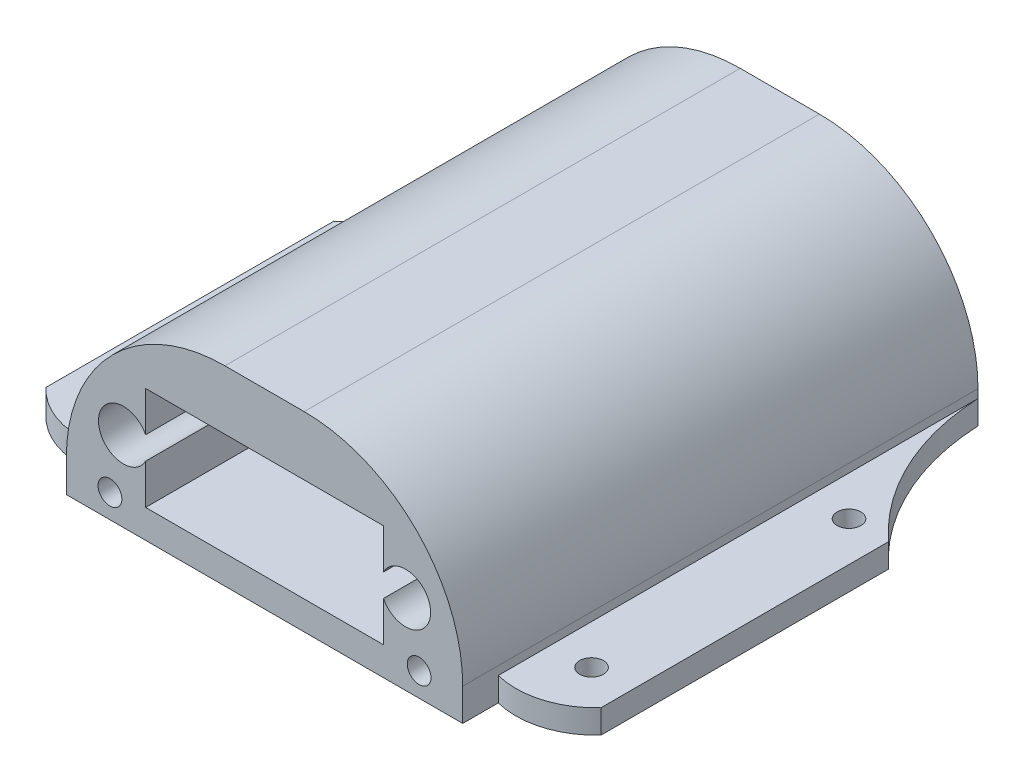
SolidWorks part; units mm, degrees
ref_plane "Front Plane" through (0, 0, 0) normal (0, 0, 1) x (1, 0, 0)
ref_plane "Top Plane" through (0, 0, 0) normal (0, 1, 0) x (1, 0, 0)
ref_plane "Right Plane" through (0, 0, 0) normal (1, 0, 0) x (0, 0, -1)
sketch "Sketch1" plane through (0, 0, 0) normal (0, 0, 1) x (1, 0, 0)
  line L0 (25, 10.1) -> (25, 3.6)
  line L1 (0, 0) -> (50, 0)
  line L2 (0, 0) -> (0, 4.0716)
  line L3 (20, 24.0716) -> (30, 24.0716)
  line L4 (50, 0) -> (50, 4.0716)
  line L10 (10, 16.6) -> (40, 16.6)
  line L11 (10, 16.6) -> (10, 3.6)
  line L12 (10, 3.6) -> (40, 3.6)
  line L13 (40, 16.6) -> (40, 3.6)
  line L14 (10, 16.6) -> (40, 3.6) construction
  line L15 (10, 3.6) -> (40, 16.6) construction
  arc A3 (30, 24.0716) -> (50, 4.0716) centre (30, 4.0716) cw
  arc A4 (0, 4.0716) -> (20, 24.0716) centre (20, 4.0716) cw
  arc A5 (40, 11.5431) -> (40, 8.6569) centre (42.8, 10.1) cw
  arc A6 (10, 11.5431) -> (10, 8.6569) centre (7.2, 10.1) ccw
  point P7 (50, 24.0716)
  point P9 (25, 10.1)
  dimension "D5" = 13
  dimension "D6" = 30
  dimension "D4" = 20
  dimension "D1" = 50
  dimension "D2" = 3.6
  dimension "D7" = 0
extrude "Boss-Extrude2" add sketch "Sketch1" along normal blind 3 contours A4 L2 L1 L4 A3 L3 L11 L10 L13 L12 | L11 | A5 L13 region at (0.5549, 2.0358, 0) region at (7.1343, 10.1, 0) region at (42.8657, 10.1, 0)
extrude "Boss-Extrude3" add sketch "Sketch1<4>" along normal blind 65 contours A4 L2 L1 L4 A3 L3 L13 A5 L12 L11 L10 region at (0.5549, 2.0358, 0)
sketch "Sketch1<4>" plane through (0, 0, 0) normal (0, 0, 1) x (1, 0, 0) same geometry as "Sketch1"
sketch "Sketch5" plane through (0, 0, 65) normal (0, 0, 1) x (1, 0, 0)
  line L0 (0, 0) -> (50, 0) construction
  circle A0 centre (5.5, 3) radius 1.5
  circle A1 centre (44.5, 3) radius 1.5
  point P0 (5.6466, 3.6791)
  dimension "D1" = 3
  dimension "D2" = 3
  dimension "D3" = 3
  dimension "D4" = 5.5
  dimension "D5" = 5.5
extrude "Cut-Extrude3" cut sketch "Sketch5" against normal blind 13
sketch "Sketch6" plane through (0, 0, 0) normal (0, -1, 0) x (-1, 0, 0)
  line L0 (-50, -65) -> (-50, 0) construction
  line L2 (-60, -21.2708) -> (-60, -57.5677)
  line L3 (0, -60.5143) -> (0, 0)
  line L6 (10, -21.2708) -> (10, -57.5677)
  line L7 (-50, 0) -> (-50, -60.5143)
  circle A0 centre (-55, -53.75) radius 1.5
  circle A1 centre (-55, -21.2708) radius 1.5
  circle A2 centre (5, -21.2708) radius 1.5
  circle A3 centre (5, -53.75) radius 1.5
  arc A4 (-50, 0) -> (-60, -21.2708) centre (-80.5646, 1.3832) cw
  arc A5 (-60, -57.5677) -> (-50, -60.5143) centre (-52.5322, -50.6661) ccw
  arc A6 (10, -57.5677) -> (0, -60.5143) centre (2.5322, -50.6661) cw
  arc A7 (0, 0) -> (10, -21.2708) centre (30.5646, 1.3832) ccw
  dimension "D2" = 3
  dimension "D3" = 10
extrude "Boss-Extrude4" add sketch "Sketch6" against normal blind 3
sketch "Sketch7" plane through (0, 0, 0) normal (0, -1, 0) x (1, 0, 0)
  line L4 (41.7, 61.55) -> (47.3, 61.55)
  line L5 (41.7, 61.55) -> (41.7, 58.45)
  line L6 (41.7, 58.45) -> (47.3, 58.45)
  line L7 (47.3, 61.55) -> (47.3, 58.45)
  line L8 (41.7, 61.55) -> (47.3, 58.45) construction
  line L9 (41.7, 58.45) -> (47.3, 61.55) construction
  line L11 (8.3, 58.45) -> (2.7, 61.55) construction
  line L12 (8.3, 61.55) -> (2.7, 58.45) construction
  line L13 (2.7, 61.55) -> (2.7, 58.45)
  line L14 (8.3, 58.45) -> (2.7, 58.45)
  line L15 (8.3, 61.55) -> (8.3, 58.45)
  line L16 (8.3, 61.55) -> (2.7, 61.55)
  dimension "D2" = 3.1
  dimension "D3" = 5.6
extrude "Cut-Extrude4" cut sketch "Sketch7" against normal blind 6
